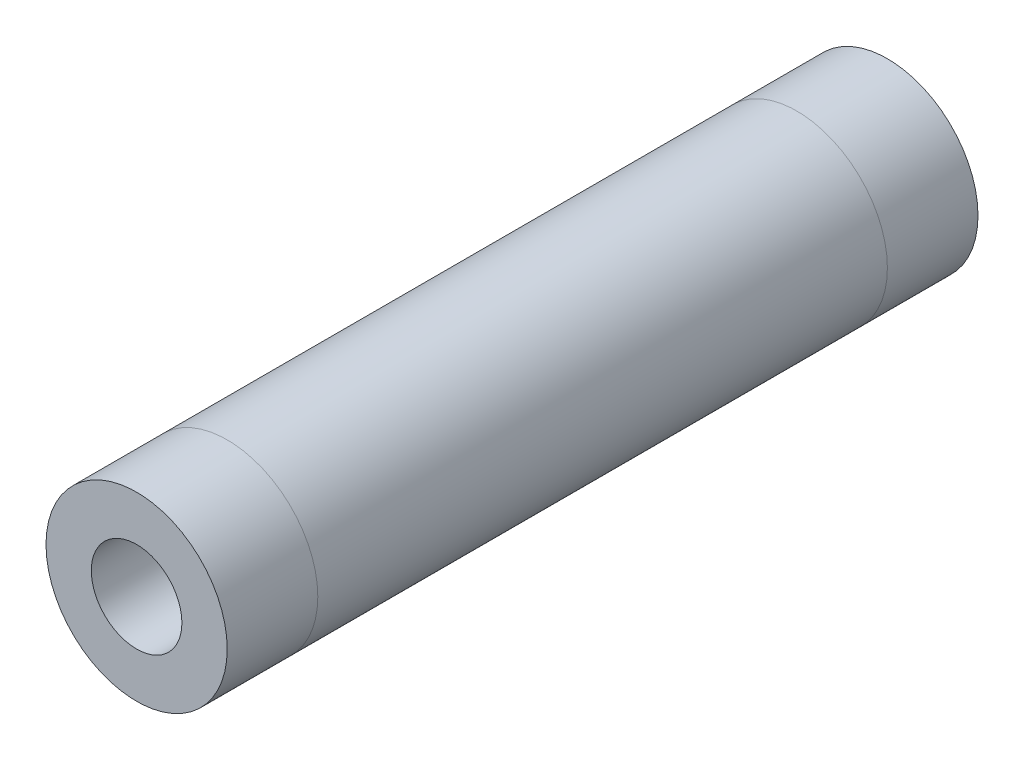
SolidWorks part; units mm, degrees
material "AISI 4130 Steel, normalized at 870C"
ref_plane "Front Plane" through (0, 0, 0) normal (0, 0, 1) x (1, 0, 0)
ref_plane "Top Plane" through (0, 0, 0) normal (0, 1, 0) x (1, 0, 0)
ref_plane "Right Plane" through (0, 0, 0) normal (1, 0, 0) x (0, 0, -1)
sketch "Axis" plane through (0, 0, 0) normal (0, 1, 0) x (1, 0, 0)
  line L0 (0, 0) -> (0, 30.48) construction
  line L1 (0, 30.48) -> (0, 83.0999) construction
  line L2 (0, 83.0999) -> (0, 113.5799) construction
  dimension "D1" = 30.48
  dimension "D3" = 52.6199
sketch "Sketch2" plane through (0, 0, 0) normal (0, 0, 1) x (1, 0, 0)
  circle A0 centre (0, 0) radius 6.35
  circle A1 centre (0, 0) radius 3.175
  circle A2 centre (0, 0) radius 4.7625
  dimension "D1" = 12.7
  dimension "D2" = 6.35
  dimension "D3" = 9.525
extrude "Threaded Insert 1-1" add sketch "Sketch2" against normal blind 6.35 from vertex contours A0 A2 | A2 A1 region at (-6.1704, 0, 0) region at (-4.6278, 0, 0) starting at point (0, 0, -30.48)
extrude "Threaded Insert 1-2" add sketch "Sketch2<5>" against normal blind 6.35 from surface contours A2 A1 region at (-4.6278, 0, 0) starting at face at (6.35, 0, -36.83)
sketch "Sketch2<5>" plane through (0, 0, 0) normal (0, 0, 1) x (1, 0, 0) same geometry as "Sketch2"
extrude "Boss-Extrude4" add sketch "Sketch2<7>" along normal blind 6.35 from vertex separate body contours A0 A2 | A2 A1 region at (-6.1704, 0, 0) region at (-4.6278, 0, 0) starting at point (0, 0, -83.0999)
sketch "Sketch2<7>" plane through (0, 0, 0) normal (0, 0, 1) x (1, 0, 0) same geometry as "Sketch2"
extrude "Boss-Extrude5" add sketch "Sketch2<8>" along normal blind 6.35 from surface contours A2 A1 region at (-4.6278, 0, 0) starting at face at (6.35, 0, -76.7499)
sketch "Sketch2<8>" plane through (0, 0, 0) normal (0, 0, 1) x (1, 0, 0) same geometry as "Sketch2"
extrude "Boss-Extrude6" add sketch "Sketch2<9>" against normal up to surface (76.7499 mm away) from surface separate body contours A0 A2 region at (-6.1704, 0, 0) up to face at (6.35, 0, -76.7499) starting at face at (4.7625, 0, -36.83)
sketch "Sketch2<9>" plane through (0, 0, 0) normal (0, 0, 1) x (1, 0, 0) same geometry as "Sketch2"
equation "\"Tube Outer Diameter\"= .5"
equation "\"Tube Inner Diameter\"= .375"
equation "\"Rod end Diameter\"= .25"
equation "\"Threaded Insert Out\"= .25"
equation "\"Threaded Insert In\"= .25'`"
equation "\"D1@Sketch2\"=\"Tube Outer Diameter\""
equation "\"D2@Sketch2\"=\"Rod end Diameter\""
equation "\"D1@Threaded Insert 1-1\" = \"Threaded Insert Out\""
equation "\"D3@Sketch2\"=\"Tube Inner Diameter\""
equation "\"D1@Threaded Insert 1-2\" = \"Threaded Insert In\""
equation "\"D1@Boss-Extrude4\"=\"Threaded Insert Out\""
equation "\"D1@Boss-Extrude5\"=\"Threaded Insert In\""
